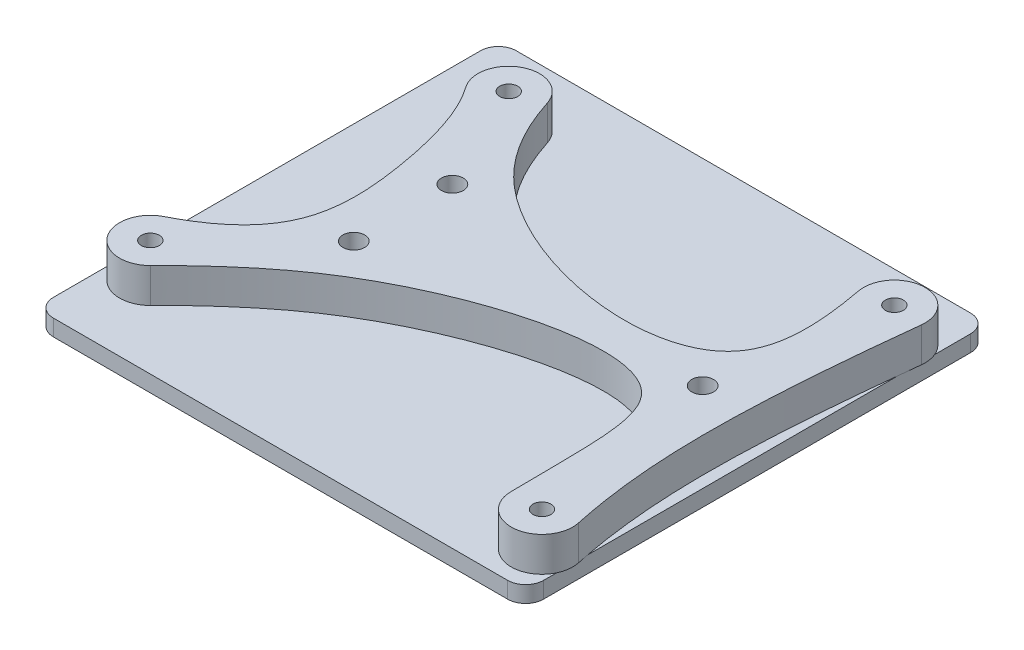
SolidWorks part; units mm, degrees
material "Alumina"
ref_plane "Front Plane" through (0, 0, 0) normal (0, 0, 1) x (1, 0, 0)
ref_plane "Top Plane" through (0, 0, 0) normal (0, 1, 0) x (1, 0, 0)
ref_plane "Right Plane" through (0, 0, 0) normal (1, 0, 0) x (0, 0, -1)
other "Center of Mass"
sketch "Sketch1" plane through (0, 0, 0) normal (0, 1, 0) x (1, 0, 0)
  line L1 (-29.0586, -55.3754) -> (60.9414, -55.3754)
  line L2 (-29.0586, -55.3754) -> (-29.0586, 29.6246)
  line L3 (-29.0586, 29.6246) -> (60.9414, 29.6246)
  line L4 (60.9414, -55.3754) -> (60.9414, 29.6246)
  dimension "D1" = 90
  dimension "D2" = 85
extrude "Boss-Extrude1" add sketch "Sketch1" along normal blind 3
sketch "Sketch3" plane through (0, 3, 0) normal (0, 1, 0) x (1, 0, 0)
  line L0 (-29.0586, -12.8754) -> (60.9414, -12.8754) construction
  line L1 (-29.0586, 29.6246) -> (-13.6586, 29.6246)
  line L2 (-29.0586, 29.6246) -> (-29.0586, 16.1246)
  line L3 (-29.0586, 16.1246) -> (-13.6586, 16.1246)
  line L4 (-13.6586, 29.6246) -> (-13.6586, 16.1246)
  line L5 (60.9414, 29.6246) -> (55.7414, 29.6246)
  line L6 (60.9414, 29.6246) -> (60.9414, 17.5246)
  line L7 (60.9414, 17.5246) -> (55.7414, 17.5246)
  line L8 (55.7414, 29.6246) -> (55.7414, 17.5246)
  line L9 (-29.0586, -55.3754) -> (-22.8586, -55.3754)
  line L10 (-29.0586, -55.3754) -> (-29.0586, -40.4754)
  line L11 (-29.0586, -40.4754) -> (-22.8586, -40.4754)
  line L12 (-22.8586, -55.3754) -> (-22.8586, -40.4754)
  line L13 (60.9414, -55.3754) -> (55.8414, -55.3754)
  line L14 (60.9414, -55.3754) -> (60.9414, -47.2754)
  line L15 (60.9414, -47.2754) -> (55.8414, -47.2754)
  line L16 (55.8414, -55.3754) -> (55.8414, -47.2754)
  line L17 (-29.0586, 29.6246) -> (-29.0586, -55.3754) construction
  line L18 (60.9414, -55.3754) -> (60.9414, 29.6246) construction
  line L19 (-24.0586, -31.9254) -> (55.9414, -31.9254)
  line L20 (-24.0586, -31.9254) -> (-24.0586, 6.1746)
  line L21 (55.9414, -31.9254) -> (55.9414, 6.1746)
  line L22 (-24.0586, 6.1746) -> (55.9414, 6.1746)
  line L23 (-24.0586, -31.9254) -> (55.9414, 6.1746) construction
  line L24 (55.9414, -31.9254) -> (-24.0586, 6.1746) construction
  line L26 (-24.0586, 6.1746) -> (-4.0586, 6.1746)
  line L27 (-24.0586, 6.1746) -> (-24.0586, -3.8254)
  line L28 (-24.0586, -3.8254) -> (-4.0586, -3.8254)
  line L29 (-4.0586, 6.1746) -> (-4.0586, -3.8254)
  circle A0 centre (-13.6586, 16.1246) radius 1.65
  circle A1 centre (55.7414, 17.5246) radius 1.65
  circle A2 centre (55.8414, -47.2754) radius 1.65
  circle A3 centre (-22.8586, -40.4754) radius 1.65
  circle A4 centre (-4.0586, -3.8254) radius 2
  circle A5 centre (-4.0586, -21.9254) radius 2
  circle A6 centre (50.9414, -12.8754) radius 2
  point P31 (15.9414, -12.8754)
  dimension "D9" = 3.3
  dimension "D10" = 3.3
  dimension "D11" = 3.3
  dimension "D12" = 3.3
  dimension "D17" = 4
  dimension "D19" = 4
  dimension "D1" = 15.4
  dimension "D2" = 13.5
  dimension "D3" = 5.2
  dimension "D4" = 12.1
  dimension "D5" = 8.1
  dimension "D6" = 5.1
  dimension "D7" = 14.9
  dimension "D8" = 6.2
  dimension "D13" = 80
  dimension "D14" = 38.1
  dimension "D15" = 10
  dimension "D16" = 20
  dimension "D18" = 5
sketch "Sketch4" plane through (0, 3, 0) normal (0, 1, 0) x (1, 0, 0)
  circle A0 centre (-4.0586, -3.8254) radius 2 construction
  circle A1 centre (-13.6586, 16.1246) radius 1.65 construction
  circle A2 centre (-4.0586, -21.9254) radius 2 construction
  circle A3 centre (50.9414, -12.8754) radius 2 construction
  circle A4 centre (55.7414, 17.5246) radius 1.65 construction
  circle A5 centre (-22.8586, -40.4754) radius 1.65 construction
  circle A6 centre (55.8414, -47.2754) radius 1.65 construction
  circle A7 centre (-4.0586, -3.8254) radius 2
  circle A8 centre (-13.6586, 16.1246) radius 1.65
  circle A9 centre (-4.0586, -21.9254) radius 2
  circle A10 centre (50.9414, -12.8754) radius 2
  circle A11 centre (55.7414, 17.5246) radius 1.65
  circle A12 centre (-22.8586, -40.4754) radius 1.65
  circle A13 centre (55.8414, -47.2754) radius 1.65
  circle A14 centre (-13.6586, 16.1246) radius 5.65
  circle A15 centre (55.7414, 17.5246) radius 5.65
  circle A16 centre (55.8414, -47.2754) radius 5.65
  circle A17 centre (-22.8586, -40.4754) radius 5.65
  circle A18 centre (-4.0586, -3.8254) radius 8
  circle A19 centre (-4.0586, -21.9254) radius 8
  circle A20 centre (50.9414, -12.8754) radius 8
  spline S0 degree 3 poles (-18.2569, 12.8417) (-14.9291, 8.1806) (-11.4742, -4.2995) (-9.9385, -23.7156) (-18.3041, -31.8351) (-25.4115, -35.435) knots 0 0 0 0 0.348076 0.653606 1 1 1 1
  spline S1 degree 3 poles (61.3563, 16.8954) (60.2028, 6.603) (58.2429, -14.0929) (58.9375, -34.7888) (61.3654, -46.0885) knots 0 0 0 0 0.477057 1 1 1 1
  spline S2 degree 3 poles (-8.2831, 17.8643) (-6.3417, 11.8655) (3.7245, -6.9347) (48.4311, -15.5323) (52.6448, 3.5523) (50.1907, 16.4701) knots 0 0 0 0 0.211563 0.7351 1 1 1 1
  spline S3 degree 3 poles (-18.8532, -44.4602) (-14.4752, -40.0597) (4.0089, -22.2236) (51.7423, -8.8428) (49.965, -31.6435) (50.192, -47.357) knots 0 0 0 0 0.247102 0.713818 1 1 1 1
  line M3 (60.9414, -55.3754) -> (60.9414, 29.6246)
  dimension "D1" = 4
  dimension "D2" = 6
extrude "Boss-Extrude2" add sketch "Sketch4" along normal blind 6.35 separate body contours S2 A14 S0 A18 | A18 A7 | A19 S3 A20 S2 A18 S0 | A19 S0 A9 | A17 S3 A19 S0 | A17 A12 | A20 S3 A16 S1 M3 | S2 A20 S1 A15 M3 | A15 A11 M3 | A20 A10 | A16 A13 M3 | A14 A8 | S1 A15 M3 | A15 M3 | A16 M3 | S1 A16 M3 region at (-11.9837, 3, -10.8962) region at (-9.4179, 3, -6.9342) region at (15.9068, 3, 13.3627) region at (3.0554, 3, 0.6913) region at (55.5089, 3, -2.9845) region at (54.5084, 3, 5.9683) region at (-2.3526, 3, 14.3411) region at (54.5945, 3, 31.0129) region at (54.1455, 3, -22.781) region at (-13.2632, 3, 32.8245) region at (54.5907, 3, 41.9256) region at (61.1221, 3, -17.5246) region at (61.0633, 3, -14.9447) region at (-19.9843, 3, 35.7976) region at (61.0576, 3, 44.8583) region at (61.1624, 3, 47.2754)
sketch "Sketch7" plane through (0, 9.35, 0) normal (0, 1, 0) x (1, 0, 0)
  line L0 (-22.8586, 16.1246) -> (-3.9987, 16.1246)
  line L1 (-13.6586, 26.2269) -> (-13.6586, 8.0086)
  line L2 (55.7414, 17.5246) -> (44.6839, 17.5246)
  line L3 (55.7414, 17.5246) -> (55.7414, 29.7098)
  line L4 (-22.8586, -40.4754) -> (-36.5042, -40.4754)
  line L5 (-22.8586, -40.4754) -> (-22.8586, -26.367)
  line L6 (55.8414, -47.2754) -> (38.6757, -47.2754)
  line L7 (55.8414, -47.2754) -> (55.8414, -59.0271)
  arc A4 (61.3563, 16.8954) -> (50.1907, 16.4701) centre (55.7414, 17.5246) ccw
  arc A5 (-8.2831, 17.8643) -> (-18.2569, 12.8417) centre (-13.6586, 16.1246) ccw
  arc A6 (-25.4115, -35.435) -> (-18.8532, -44.4602) centre (-22.8586, -40.4754) ccw
  arc A7 (50.192, -47.357) -> (61.3654, -46.0885) centre (55.8414, -47.2754) ccw
  arc A8 (61.3563, 16.8954) -> (50.1907, 16.4701) centre (55.7414, 17.5246) ccw
  arc A9 (-8.2831, 17.8643) -> (-18.2569, 12.8417) centre (-13.6586, 16.1246) ccw
  arc A10 (-25.4115, -35.435) -> (-18.8532, -44.4602) centre (-22.8586, -40.4754) ccw
  arc A11 (50.192, -47.357) -> (61.3654, -46.0885) centre (55.8414, -47.2754) ccw
  spline S4 degree 3 poles (2791.9216, -1271.8289) (157.9023, -276.9245) (-78.7891, 25.0266) (249.5702, 326.9824) (-1356.7862, 2639.5985) knots -5.849865 -5.849865 -5.849865 -5.849865 0.522943 8.740126 8.740126 8.740126 8.740126 only from (61.3654, -46.0885) to (61.3563, 16.8954)
  spline S5 degree 3 poles (-805.6301, 2890.6823) (-121.7329, 262.3096) (136.9067, -32.5472) (-142.2506, 21.1381) (354.0254, 425.1104) (-2843.9296, -922.3003) knots -1.979032 -1.979032 -1.979032 -1.979032 0.2649 0.788437 4.265187 4.265187 4.265187 4.265187 only from (50.1907, 16.4701) to (-8.2831, 17.8643)
  spline S6 degree 3 poles (-1473.8256, -2605.3055) (-127.2381, 139.2026) (-16.9997, 65.5573) (-1.6523, -128.4753) (-798.3741, 144.6264) (-2363.2601, -1826.4076) knots -3.597884 -3.597884 -3.597884 -3.597884 0.348076 0.653606 6.395513 6.395513 6.395513 6.395513 only from (-18.2569, 12.8417) to (-25.4115, -35.435)
  spline S7 degree 3 poles (570.6364, 2896.0882) (38.3119, -254.8051) (-110.9815, -54.4582) (145.1312, 17.3364) (-213.9532, -372.137) (2210.9328, -2091.5365) knots -2.409016 -2.409016 -2.409016 -2.409016 0.247102 0.713818 2.95647 2.95647 2.95647 2.95647 only from (-18.8532, -44.4602) to (50.192, -47.357)
  spline S8 degree 3 poles (61.3654, -46.0885) (58.9375, -34.7888) (58.2429, -14.0929) (60.2028, 6.603) (61.3563, 16.8954) knots 0 0 0 0 0.522943 1 1 1 1
  spline S9 degree 3 poles (50.1907, 16.4701) (52.6448, 3.5523) (48.4311, -15.5323) (3.7245, -6.9347) (-6.3417, 11.8655) (-8.2831, 17.8643) knots 0 0 0 0 0.2649 0.788437 1 1 1 1
  spline S10 degree 3 poles (-18.2569, 12.8417) (-14.9291, 8.1806) (-11.4742, -4.2995) (-9.9385, -23.7156) (-18.3041, -31.8351) (-25.4115, -35.435) knots 0 0 0 0 0.348076 0.653606 1 1 1 1
  spline S11 degree 3 poles (-18.8532, -44.4602) (-14.4752, -40.0597) (4.0089, -22.2236) (51.7423, -8.8428) (49.965, -31.6435) (50.192, -47.357) knots 0 0 0 0 0.247102 0.713818 1 1 1 1
  dimension "D1" = 0
extrude "Cut-Extrude1" cut sketch "Sketch4<3>" against normal through all contours A8 | A11 | A13 | A12 region at (-13.6586, 3, -16.1246) region at (55.7414, 3, -17.5246) region at (-22.8586, 3, 40.4754) region at (55.8414, 3, 47.2754)
sketch "Sketch4<3>" plane through (0, 3, 0) normal (0, 1, 0) x (1, 0, 0) same geometry as "Sketch4"
fillet "Fillet1" radius 3.3 4 edges at (-29.0586, 1.5, 55.3754) (60.9414, 1.5, 55.3754) (60.9414, 1.5, -29.6246) (-29.0586, 1.5, -29.6246)
